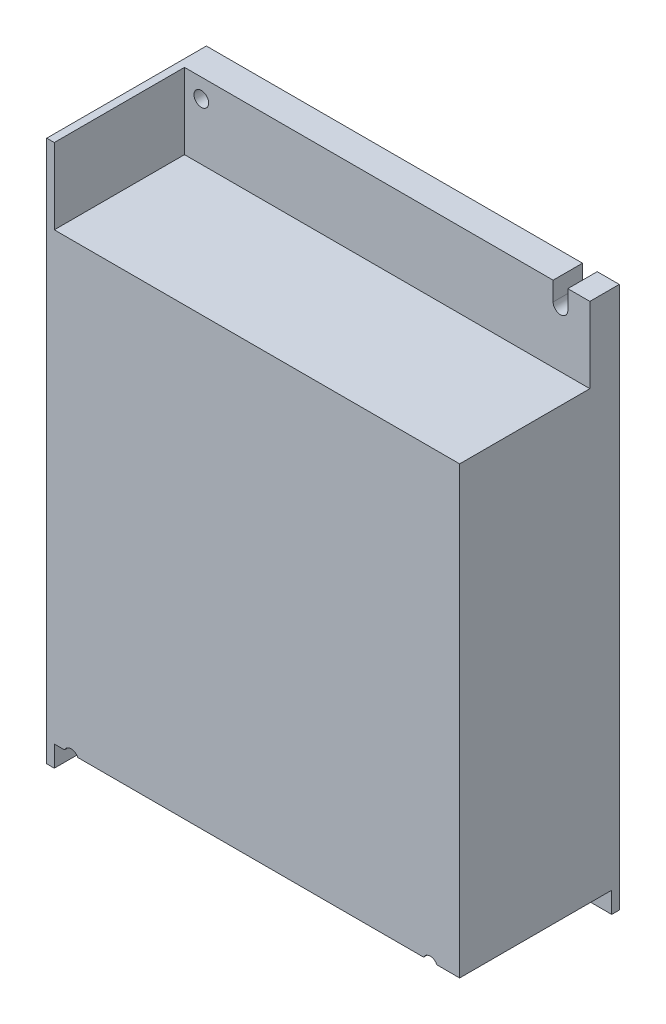
SolidWorks part; units mm, degrees
ref_plane "前视基准面" through (0, 0, 0) normal (0, 0, 1) x (1, 0, 0)
ref_plane "上视基准面" through (0, 0, 0) normal (0, 1, 0) x (1, 0, 0)
ref_plane "右视基准面" through (0, 0, 0) normal (1, 0, 0) x (0, 0, -1)
sketch "草图1" plane through (0, 0, 0) normal (0, 0, 1) x (1, 0, 0)
  line L1 (-49.15, 64.5) -> (49.15, 64.5)
  line L2 (-49.15, 64.5) -> (-49.15, -64.5)
  line L3 (-49.15, -64.5) -> (49.15, -64.5)
  line L4 (49.15, 64.5) -> (49.15, -64.5)
  line L5 (-49.15, 64.5) -> (49.15, -64.5) construction
  line L6 (-49.15, -64.5) -> (49.15, 64.5) construction
  point P0 (0, 0)
  dimension "D1" = 98.3
  dimension "D2" = 129
extrude "凸台-拉伸1" add sketch "草图1" along normal blind 38
sketch "草图2" plane through (0, 0, 38) normal (0, 0, 1) x (1, 0, 0)
  line L2 (49.15, 64.5) -> (-49.15, 64.5) construction
  line L3 (-47.35, 64.5) -> (49.15, 64.5)
  line L4 (-47.35, 64.5) -> (-47.35, 46.5)
  line L5 (-47.35, 46.5) -> (49.15, 46.5)
  line L6 (49.15, 64.5) -> (49.15, 46.5)
  line L7 (49.15, -64.5) -> (49.15, 64.5) construction
  line L8 (-49.15, 64.5) -> (-49.15, -64.5) construction
  dimension "D1" = 1.8
  dimension "D2" = 18
extrude "切除-拉伸1" cut sketch "草图2" against normal offset from surface (31 mm away) 7 up to face at (0, 0, 0)
sketch "草图3" plane through (0, 0, 38) normal (0, 0, 1) x (1, 0, 0)
  line L1 (-49.15, 64.5) -> (-49.15, -64.5) construction
  line L2 (-47.35, -59.5) -> (49.15, -59.5)
  line L3 (-47.35, -59.5) -> (-47.35, -64.5)
  line L4 (-47.35, -64.5) -> (49.15, -64.5)
  line L5 (49.15, -59.5) -> (49.15, -64.5)
  dimension "D1" = 1.8
  dimension "D2" = 5
extrude "切除-拉伸2" cut sketch "草图3" against normal offset from surface (36.2 mm away) 1.8 up to face at (0, 0, 0)
sketch "草图4" plane through (0, 0, 0) normal (0, 0, -1) x (-1, 0, 0)
  line L0 (-49.15, -59.5) -> (-49.15, 46.5) construction
  line L1 (43.35, 60) -> (-42.15, 60) construction
  line L2 (43.35, 60) -> (43.35, -61.5) construction
  line L3 (43.35, -61.5) -> (-42.15, -61.5) construction
  line L4 (-42.15, 60) -> (-42.15, -61.5) construction
  line L5 (47.35, 64.5) -> (-49.15, 64.5) construction
  line L7 (-40.4, 60) -> (-40.4, 64.5)
  line L8 (-40.4, 64.5) -> (-43.9, 64.5)
  line L9 (-43.9, 64.5) -> (-43.9, 60)
  line L10 (43.35, -60.25) -> (-42.15, -60.25) construction
  line L11 (-40.4, -60.25) -> (-40.4, -64.5)
  line L12 (-49.15, -64.5) -> (47.35, -64.5) construction
  line L13 (-40.4, -64.5) -> (-43.9, -64.5)
  line L14 (-43.9, -64.5) -> (-43.9, -60.25)
  line L15 (43.35, -61.5) -> (43.35, -60.25) construction
  line L16 (41.6, -61.5) -> (41.6, -60.25)
  line L17 (45.1, -61.5) -> (45.1, -60.25)
  arc A0 (41.6, -61.5) -> (45.1, -61.5) centre (43.35, -61.5) ccw
  circle A1 centre (43.35, 60) radius 1.75
  arc A2 (45.1, -60.25) -> (41.6, -60.25) centre (43.35, -60.25) ccw
  arc A4 (-40.4, 60) -> (-43.9, 60) centre (-42.15, 60) cw
  arc A5 (-40.4, -60.25) -> (-43.9, -60.25) centre (-42.15, -60.25) ccw
  point P0 (0, 0)
  point P19 (43.35, -60.875)
  dimension "D5" = 3.5
  dimension "D6" = 1.75
  dimension "D8" = 1.75
  dimension "D9" = 1.75
  dimension "D1" = 85.5
  dimension "D2" = 121.5
  dimension "D3" = 7
  dimension "D4" = 4.5
  dimension "D7" = 1.25
extrude "切除-拉伸3" cut sketch "草图4" against normal through all
